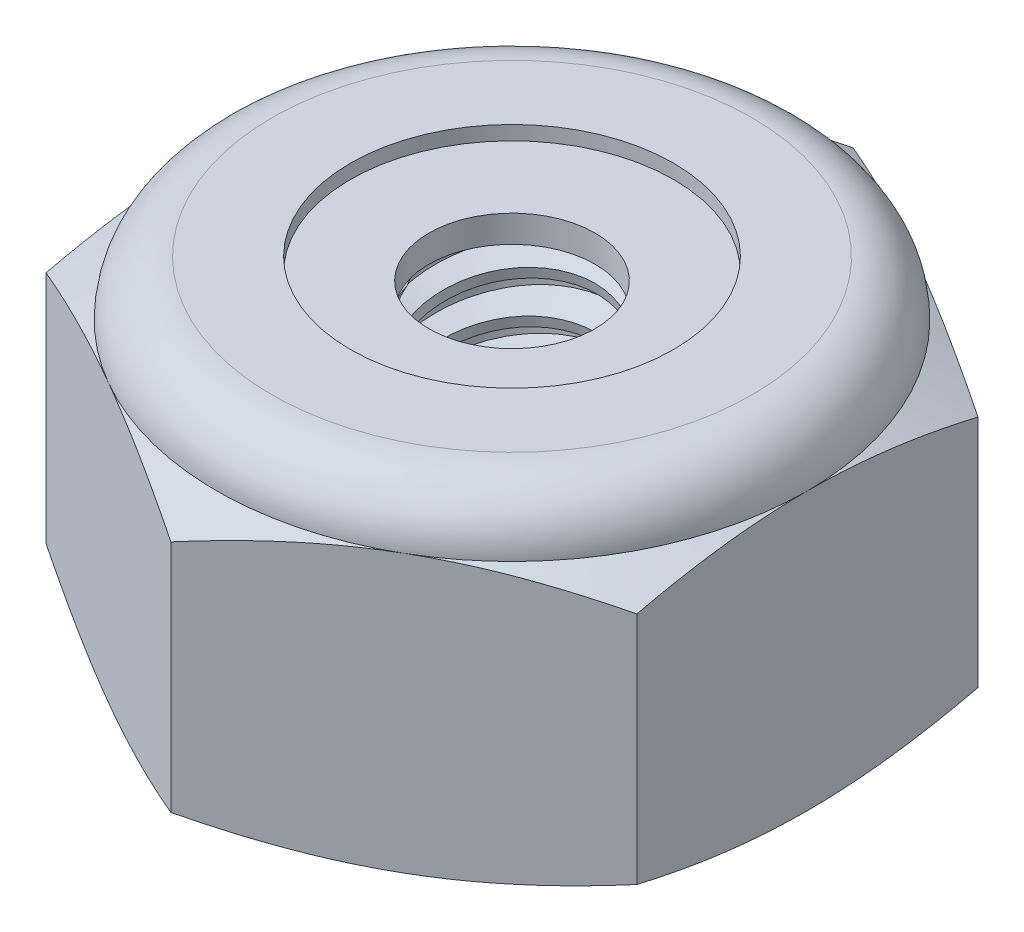
SolidWorks part; units mm, degrees
ref_plane "Front" through (0, 0, 0) normal (0, 0, 1) x (1, 0, 0)
ref_plane "Top" through (0, 0, 0) normal (0, 1, 0) x (1, 0, 0)
ref_plane "Right" through (0, 0, 0) normal (1, 0, 0) x (0, 0, -1)
sketch "Sketch1" plane through (0, 0, 0) normal (0, 1, 0) x (1, 0, 0)
  line L1 (0, 3.6662) -> (-3.175, 1.8331)
  line L2 (-3.175, 1.8331) -> (-3.175, -1.8331)
  line L3 (-3.175, -1.8331) -> (0, -3.6662)
  line L4 (0, -3.6662) -> (3.175, -1.8331)
  line L5 (3.175, -1.8331) -> (3.175, 1.8331)
  line L6 (3.175, 1.8331) -> (0, 3.6662)
  circle A0 centre (0, 0) radius 3.175 construction
  dimension "Hex Flats" = 6.35
extrude "Extrude1" add sketch "Sketch1" along normal blind 3.5719
sketch "Sketch2" plane through (0, 0, 0) normal (1, 0, 0) x (0, 0, -1)
  line L0 (-1.0922, 0) -> (-1.0922, 3.5719) construction
  line L1 (0, 0) -> (1.0922, 0)
  line L2 (0, 0) -> (0, 3.5719)
  line L3 (0, 3.5719) -> (1.0922, 3.5719)
  line L4 (1.0922, 0) -> (1.0922, 3.5719)
  line L5 (-1.8331, 3.5719) -> (1.8331, 3.5719) construction
  line L7 (0, -1.0922) -> (0, 0) construction
  dimension "Thread Dia" = 2.1844
revolve "Revolve1" add sketch "Sketch2" angle 360 about L7
sketch "Sketch3" plane through (0, 0, 0) normal (1, 0, 0) x (0, 0, -1)
  line L0 (1.0922, 3.5719) -> (-1.0922, 3.5719) construction
  line L1 (-1.0922, 3.5719) -> (-1.0922, 3.1183) construction
  line L2 (-1.0922, 3.1183) -> (1.0922, 3.5719) construction
  line L3 (1.0922, 3.5719) -> (1.1037, 3.5164) construction
  line L4 (1.1037, 3.5164) -> (1.1844, 3.1278)
  line L5 (1.1844, 3.1278) -> (0.9152, 3.2166)
  line L6 (0.9152, 3.2166) -> (0.8922, 3.3277)
  line L7 (0.8922, 3.3277) -> (1.1037, 3.5164)
  line L8 (0.9037, 3.2722) -> (1.1441, 3.3221) construction
  line L9 (1.0922, 3.5719) -> (1.0922, 3.3113) construction
  line L10 (1.0922, 3.3113) -> (-1.0922, 2.8577) construction
  line L11 (-1.0922, 2.8577) -> (-1.0922, 3.1183) construction
  line L12 (-0.1012, 3.5719) -> (0.1012, 2.5972) construction
  line L13 (-1.0922, 0) -> (-1.0922, 3.5719) construction
  line L14 (0, 3.5719) -> (1.0922, 3.5719) construction
  line L15 (1.0922, 0) -> (1.0922, 3.5719) construction
  point P13 (0, 3.0845)
  dimension "D1" = 0.0567
  dimension "D2" = 0.1134
  dimension "Thread Pitch" = 0.4536
  dimension "D4" = 60
  dimension "D5" = 0.4536
revolve "Cut-Revolve1" cut sketch "Sketch3" angle 360 about L12
pattern_linear "LPattern1" count 8 spacing 0.4536 along (0, -1, 0) count 2 spacing 0.4536 along (0, 1, 0) of "Cut-Revolve1"
sketch "Sketch4" plane through (0, 0, 0) normal (1, 0, 0) x (0, 0, -1)
  line L0 (0, 3.5719) -> (1.0922, 3.5719)
  line L1 (1.0922, 3.5719) -> (0.8922, 3.4786)
  line L2 (0.8922, 3.4786) -> (0.8922, 0.0933)
  line L3 (0.8922, 0.0933) -> (1.0922, 0)
  line L4 (1.0922, 0) -> (0, 0)
  line L5 (0, 0) -> (0, 3.5719)
  line L6 (1.0922, 0) -> (1.0922, 3.5719) construction
  line L7 (0, 3.5719) -> (1.0922, 3.5719) construction
  line L8 (0, 0) -> (1.0922, 0) construction
  line L9 (0, 0) -> (0, 3.5719) construction
  line L10 (0, 3.5719) -> (0, 3.7926) construction
  dimension "D1" = 25
revolve "Cut-Revolve2" cut sketch "Sketch4" angle 360 about L10
combine bodies "Combine1" operation type subtract main body 112 bodies to subtract 111
sketch "Sketch5" plane through (0, 0, 0) normal (1, 0, 0) x (0, 0, -1)
  line L0 (0, 0) -> (3.175, 0)
  line L1 (3.175, 0) -> (3.6662, 0.229)
  line L2 (3.6662, 0.229) -> (3.6662, 2.7475)
  line L3 (3.6662, 2.7475) -> (3.175, 2.9766)
  line L4 (2.5797, 3.5719) -> (2.5797, 4.8419)
  line L5 (2.5797, 4.8419) -> (4.9362, 4.8419)
  line L6 (4.9362, 4.8419) -> (4.9362, -1.27)
  line L7 (4.9362, -1.27) -> (0, -1.27)
  line L8 (0, -1.27) -> (0, 0)
  line L9 (3.175, 2.9766) -> (3.175, 0) construction
  line L10 (0, 0) -> (1.0922, 0) construction
  line L13 (3.6662, 1.4883) -> (4.9362, 1.4883) construction
  line L14 (3.6662, 3.5719) -> (3.6662, 0) construction
  line L15 (0, 0) -> (0, 4.8419) construction
  line L20 (0, 4.8419) -> (2.5797, 4.8419) construction
  line L22 (0, 3.5719) -> (1.0922, 3.5719) construction
  arc A0 (3.175, 2.9766) -> (2.5797, 3.5719) centre (2.5797, 2.9766) ccw
  dimension "D1" = 25
  dimension "D2" = 1.27
  dimension "D3" = 3.5719
  dimension "D4" = 0.5953
revolve "Cut-Revolve3" cut sketch "Sketch5" angle 360 about L15
sketch "Sketch6" plane through (0, 0, 0) normal (1, 0, 0) x (0, 0, -1)
  line L0 (0, 2.9766) -> (3.0226, 2.9766)
  line L1 (2.5797, 3.4195) -> (1.7359, 3.4195)
  line L2 (0, 4.8419) -> (0, 2.9766)
  line L3 (1.7359, 4.8419) -> (0, 4.8419)
  line L4 (0, 4.8419) -> (2.5797, 4.8419) construction
  line L5 (0, 0) -> (0, 4.8419) construction
  line L6 (0, 4.8419) -> (0, 44.323) construction
  line L7 (1.7359, 3.4195) -> (1.7359, 4.8419)
  line L8 (2.5797, 3.5719) -> (2.5797, 3.4195) construction
  line L9 (1.7359, 3.4195) -> (0.8922, 3.4195) construction
  line L10 (0.8922, 3.4195) -> (0.8922, 3.4786) construction
  arc A0 (3.0226, 2.9766) -> (2.5797, 3.4195) centre (2.5797, 2.9766) ccw
  arc A1 (3.175, 2.9766) -> (2.5797, 3.5719) centre (2.5797, 2.9766) ccw construction
  dimension "D1" = 0.1524
revolve "Cut-Revolve4" cut sketch "Sketch6" angle 360 about L6
sketch "Sketch7" plane through (0, 0, 0) normal (1, 0, 0) x (0, 0, -1)
  line L0 (0.8922, 3.0528) -> (2.9384, 3.0528)
  line L1 (2.5797, 3.3433) -> (0.8922, 3.3433)
  line L2 (0.8922, 3.3433) -> (0.8922, 3.0528)
  line L3 (0.8922, 3.0528) -> (0, 3.0528) construction
  line L4 (0, 3.0528) -> (0, 3.3433) construction
  line L5 (0, 3.3433) -> (0.8922, 3.3433) construction
  line L6 (0.8922, 3.0528) -> (0.8922, 2.9766) construction
  line L7 (0, 2.9766) -> (3.0226, 2.9766) construction
  line L8 (2.5797, 3.3433) -> (2.5797, 3.4195) construction
  arc A0 (2.9384, 3.0528) -> (2.5797, 3.3433) centre (2.5797, 2.9766) ccw
  arc A2 (3.0226, 2.9766) -> (2.5797, 3.4195) centre (2.5797, 2.9766) ccw construction
  dimension "D1" = 0.0762
revolve "Revolve2" add sketch "Sketch7" angle 360 about L4
equation "\"D1@Sketch3\"=\"Thread Pitch@Sketch3\"/8"
equation "\"D2@Sketch3\"=\"Thread Pitch@Sketch3\"/4"
equation "\"D5@Sketch3\"=\"Thread Pitch@Sketch3\""
equation "\"D4@LPattern1\"=\"Thread Pitch@Sketch3\""
equation "\"D3@LPattern1\"=\"Thread Pitch@Sketch3\""
equation "\"D1@LPattern1\"=\"Height@Extrude1\"/\"Thread Pitch@Sketch3\""
equation "\"D4@Sketch5\"=\"Height@Extrude1\"/6"
